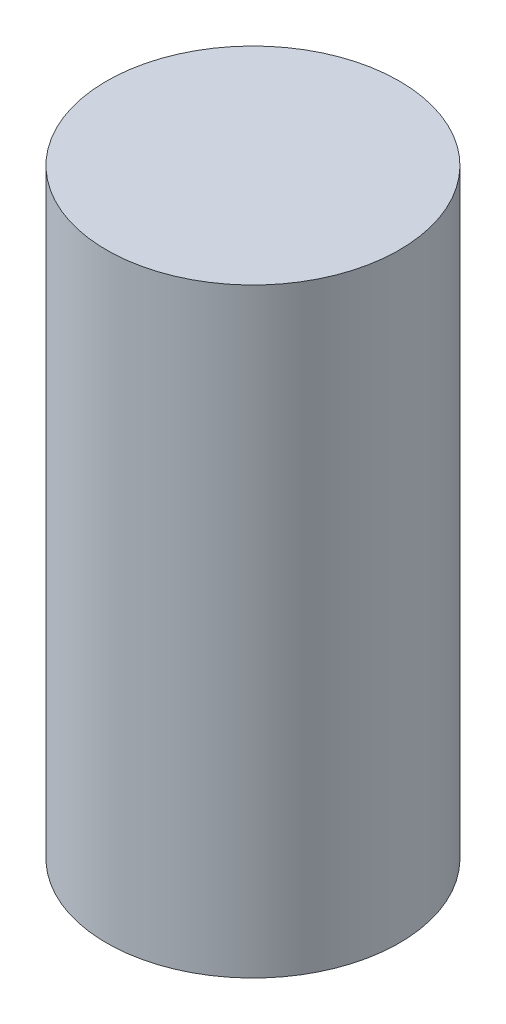
SolidWorks part; units mm, degrees
ref_plane "Front Plane" through (0, 0, 0) normal (0, 0, 1) x (1, 0, 0)
ref_plane "Top Plane" through (0, 0, 0) normal (0, 1, 0) x (1, 0, 0)
ref_plane "Right Plane" through (0, 0, 0) normal (1, 0, 0) x (0, 0, -1)
sketch "Sketch1" plane through (0, 0, 0) normal (0, 1, 0) x (1, 0, 0)
  circle A0 centre (0, 0) radius 200
extrude "Boss-Extrude1" add sketch "Sketch1" along normal blind 820
